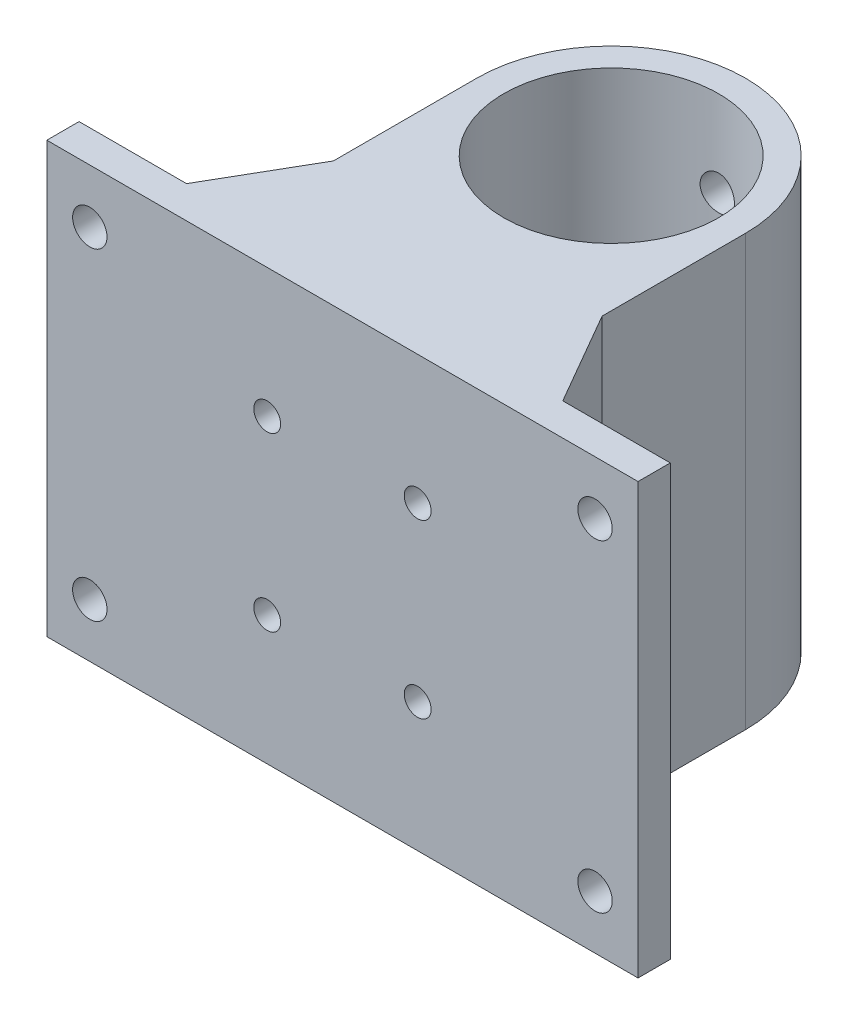
SolidWorks part; units mm, degrees
material "6061 合金"
ref_plane "前视基准面" through (0, 0, 0) normal (0, 0, 1) x (1, 0, 0)
ref_plane "上视基准面" through (0, 0, 0) normal (0, 1, 0) x (1, 0, 0)
ref_plane "右视基准面" through (0, 0, 0) normal (1, 0, 0) x (0, 0, -1)
sketch "草图1" plane through (0, 0, 0) normal (0, 1, 0) x (1, 0, 0)
  line L2 (-12.5, -25) -> (12.5, -25)
  line L3 (-12.5, -25) -> (-12.5, 0)
  line L5 (12.5, -25) -> (12.5, 0)
  arc A0 (12.5, 0) -> (-12.5, 0) centre (0, 0) ccw
  circle A1 centre (0, 0) radius 10
  point P3 (0, -12.5)
  dimension "D1" = 25
  dimension "D3" = 20
extrude "凸台-拉伸1" add sketch "草图1" along normal mid plane 40
sketch "草图7" plane through (0, 0, 0) normal (0, 0, 1) x (1, 0, 0)
  line L0 (0, 0) -> (9.3494, 0) construction
  line L1 (0, -12) -> (0, 12) construction
  line L2 (0, 0) -> (-12.5, 0) construction
  line L3 (-12.5, 20) -> (-12.5, -20) construction
  circle A0 centre (0, -12) radius 1.6
  circle A1 centre (0, 12) radius 1.6
  dimension "D1" = 12
extrude "切除-拉伸2" cut sketch "草图7" against normal through all
hole_wizard "M3 螺纹孔1" positions "3D草图1" profile "草图8" tap size "M3" standard "GB"
sketch3d "3D草图1"
  point P0 (-7, -8, 25)
  point P7 (7, -8, 25)
  point P9 (7, 8, 25)
  point P11 (-7, 8, 25)
sketch "草图8" plane through (-7, -8, 25) normal (1, 0, 0) x (0, -1, 0)
  line L0 (0, 0) -> (0, 10.2511)
  line L1 (0, 10.2511) -> (1.25, 9.5)
  line L2 (1.25, 9.5) -> (1.25, 0)
  line L5 (1.25, 0) -> (0, 0)
  line L10 (0, 10.2511) -> (-1.25, 9.5) construction
  line L11 (0, -6.35) -> (0, 107.95) construction
  dimension "螺纹孔钻头直径" = 2.5
  dimension "螺纹孔钻头深度" = 9.5
  dimension "导头角度" = 118
cosmetic thread "孔螺蚊线1" parameters "D1"=8, "D2"=3
cosmetic thread "孔螺蚊线2" parameters "D1"=8, "D2"=3
cosmetic thread "孔螺蚊线3" parameters "D1"=8, "D2"=3
cosmetic thread "孔螺蚊线4" parameters "D1"=8, "D2"=3
sketch "草图9" plane through (12.5, 0, 0) normal (1, 0, 0) x (0, 0, -1)
  line L0 (-25, 20) -> (0, 20) construction
  line L1 (-25, -20) -> (-22, -20)
  line L2 (-25, -20) -> (-25, 20)
  line L3 (-25, 20) -> (-22, 20)
  line L4 (-22, -20) -> (-22, 20)
  dimension "D1" = 3
extrude "凸台-拉伸2" add sketch "草图9" along normal blind 15
sketch "草图10" plane through (0, 0, 22) normal (0, 0, -1) x (-1, 0, 0)
  line L0 (-12.5, 0) -> (-27.5, 0) construction
  line L3 (-12.5, -20) -> (-12.5, 20) construction
  line L4 (-27.5, -20) -> (-27.5, 20) construction
  line L5 (-27.5, 20) -> (-12.5, 20) construction
  circle A0 centre (-23.5, 15) radius 1.6
  circle A1 centre (-23.5, -15) radius 1.6
  dimension "D1" = 4
  dimension "D2" = 3.2
  dimension "D3" = 5
extrude "切除-拉伸3" cut sketch "草图10" against normal through all
ref_plane "基准面1" through (0, 0, 0) normal (1, 0, 0) x (0, 0, -1)
mirror "镜向6" about plane through (0, 0, 0) normal (1, 0, 0) of "切除-拉伸3", "凸台-拉伸2"
chamfer "倒角1" distance 5 angle 60 2 edges at (12.5, 0, 22) (-12.5, 0, 22) first distance on face at (25.1, -15, 22) first distance on face at (-25.1, -15, 22)
